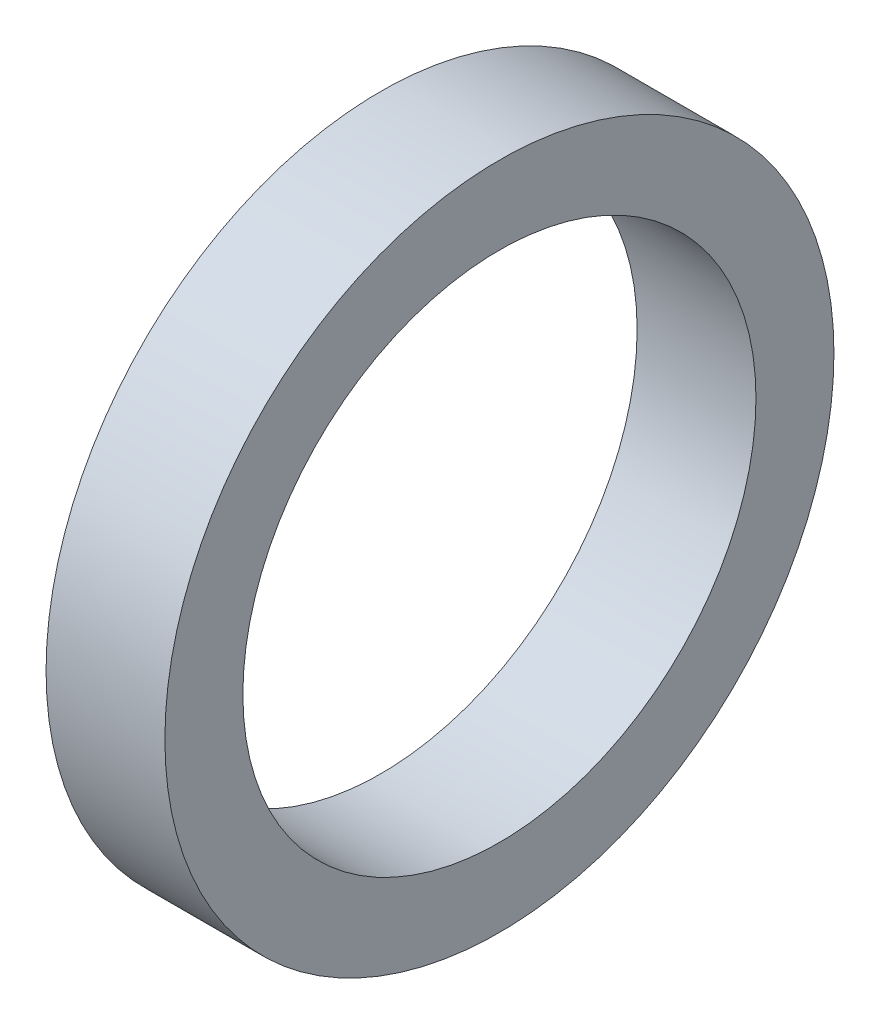
SolidWorks part; units mm, degrees
ref_plane "Front Plane" through (0, 0, 0) normal (0, 0, 1) x (1, 0, 0)
ref_plane "Top Plane" through (0, 0, 0) normal (0, 1, 0) x (1, 0, 0)
ref_plane "Right Plane" through (0, 0, 0) normal (1, 0, 0) x (0, 0, -1)
sketch "Sketch1" plane through (0, 0, 0) normal (1, 0, 0) x (0, 0, -1)
  circle A0 centre (0, 0) radius 3.2385
  circle A1 centre (0, 0) radius 4.2227
  dimension "D1" = 6.477
  dimension "D2" = 8.4455
extrude "Boss-Extrude1" add sketch "Sketch1" along normal blind 1.5
equation "\"D1@Boss-Extrude1\"=1.5mm"
